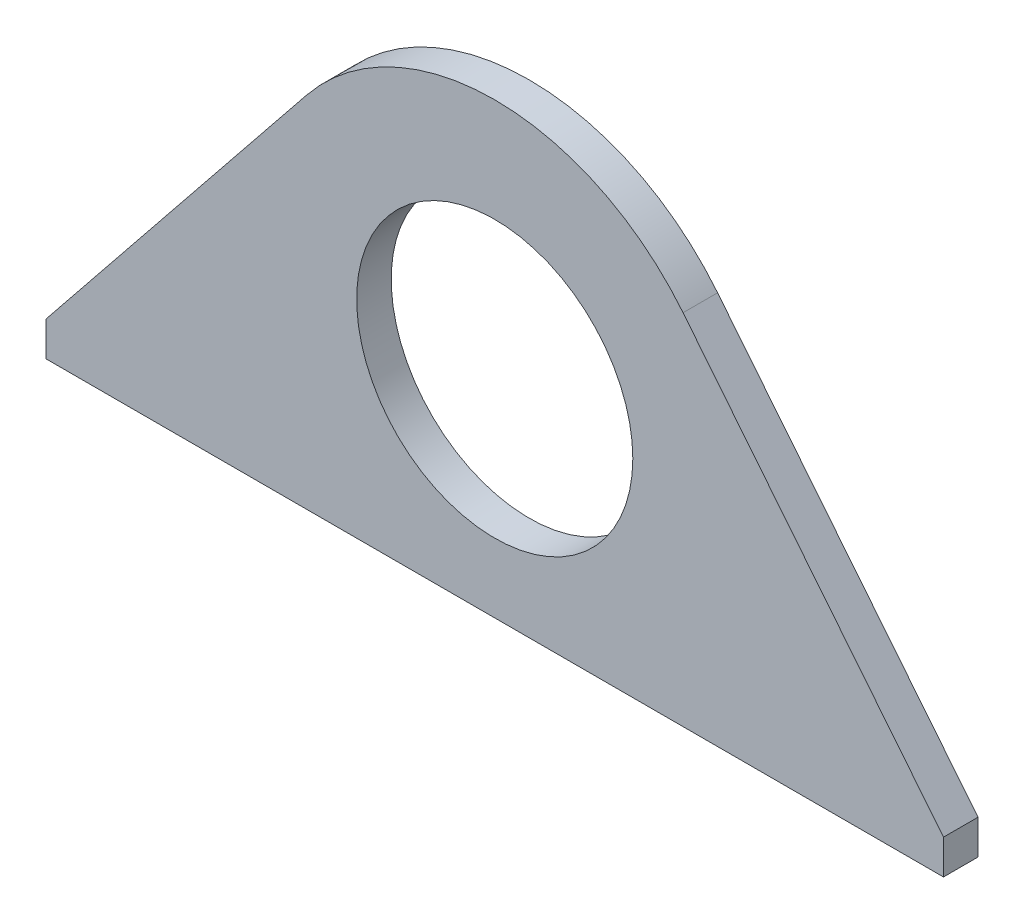
SolidWorks part; units mm, degrees
material "AISI 304"
ref_plane "Спереди" through (0, 0, 0) normal (0, 0, 1) x (1, 0, 0)
ref_plane "Сверху" through (0, 0, 0) normal (0, 1, 0) x (1, 0, 0)
ref_plane "Справа" through (0, 0, 0) normal (1, 0, 0) x (0, 0, -1)
sketch "Эскиз1" plane through (0, 0, 0) normal (0, 0, 1) x (1, 0, 0)
  line L0 (-65, 5) -> (-27.2798, 51.9275)
  line L1 (-65, 0) -> (65, 0)
  line L2 (-65, 0) -> (-65, 5)
  line L4 (65, 0) -> (65, 5)
  line L5 (27.2798, 51.9275) -> (65, 5)
  line L6 (0, 0) -> (0, 84.6489) construction
  arc A0 (-27.2798, 51.9275) -> (27.2798, 51.9275) centre (0, 30) cw
  circle A1 centre (0, 30) radius 20
  point P10 (0, 0)
  dimension "D1" = 35
  dimension "D3" = 40
  dimension "D4" = 5
  dimension "D2" = 130
  dimension "D5" = 5
  dimension "D6" = 30
extrude "Бобышка-Вытянуть1" add sketch "Эскиз1" along normal blind 2.5 and the other way blind 2.5
